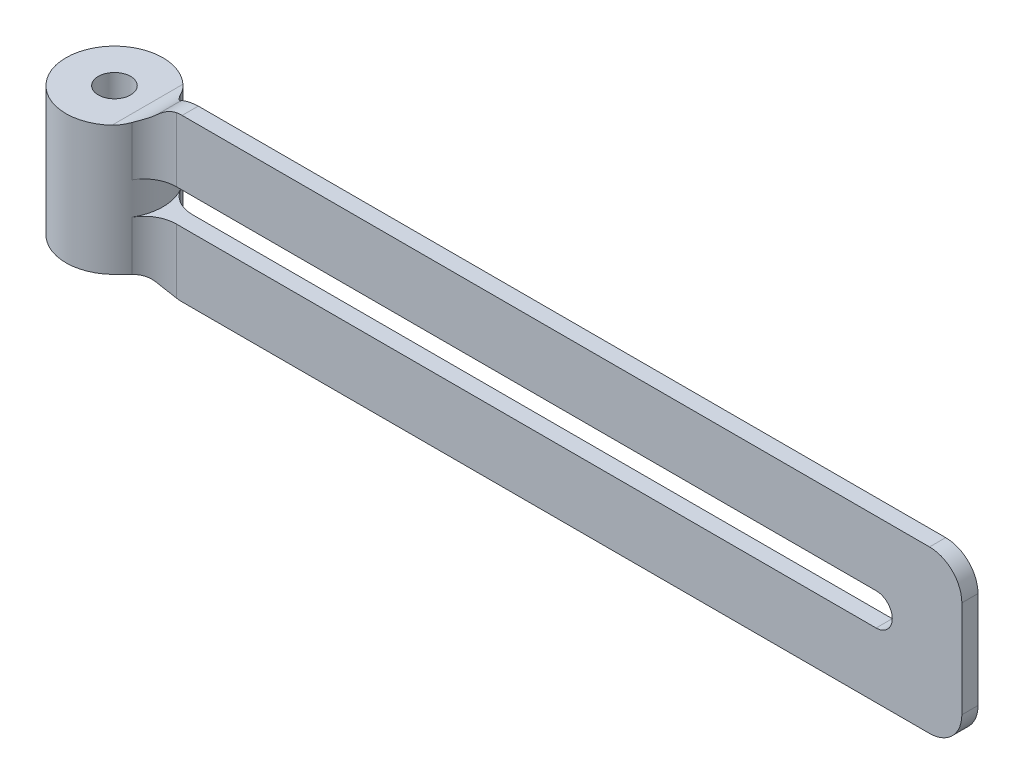
SolidWorks part; units mm, degrees
ref_plane "Front Plane" through (0, 0, 0) normal (0, 0, 1) x (1, 0, 0)
ref_plane "Top Plane" through (0, 0, 0) normal (0, 1, 0) x (1, 0, 0)
ref_plane "Right Plane" through (0, 0, 0) normal (1, 0, 0) x (0, 0, -1)
sketch "Sketch1" plane through (0, 0, 0) normal (0, 0, 1) x (1, 0, 0)
  line L1 (700, 2.5907) -> (0, 2.5907)
  line L2 (700, 2.5907) -> (700, 52.5907)
  line L3 (700, 52.5907) -> (0, 52.5907)
  line L4 (0, 2.5907) -> (0, 52.5907)
  dimension "D1" = 700
  dimension "D2" = 50
extrude "Boss-Extrude1" add sketch "Sketch1" along normal blind 5
fillet "Fillet1" radius 10 4 edges at (700, 2.5907, 2.5) (700, 52.5907, 2.5) (0, 2.5907, 2.5) (0, 52.5907, 2.5)
sketch "Sketch2" plane through (0, 0, 5) normal (0, 0, 1) x (1, 0, 0)
  line L0 (23.4634, 27.5907) -> (673.4634, 27.5907) construction
  line L1 (23.4634, 32.5907) -> (673.4634, 32.5907)
  line L2 (23.4634, 22.5907) -> (673.4634, 22.5907)
  line L3 (690, 52.5907) -> (10, 52.5907) construction
  arc A0 (23.4634, 32.5907) -> (23.4634, 22.5907) centre (23.4634, 27.5907) ccw
  arc A1 (673.4634, 22.5907) -> (673.4634, 32.5907) centre (673.4634, 27.5907) ccw
  point P2 (348.4634, 27.5907)
  dimension "D1" = 650
  dimension "D2" = 10
  dimension "D3" = 25
extrude "Cut-Extrude1" cut sketch "Sketch2" against normal blind 150
sketch "Sketch5" plane through (0, 0, 0) normal (0, 0, -1) x (-1, 0, 0)
  line L0 (-690, 52.5907) -> (-450, 52.5907)
  line L1 (-690, 52.5907) -> (-10, 52.5907) construction
  line L2 (-450, 52.5907) -> (-450, 2.5907)
  line L3 (-10, 2.5907) -> (-690, 2.5907) construction
  line L4 (-450, 2.5907) -> (-714.3563, 2.5907)
  line L5 (-714.3563, 2.5907) -> (-714.3563, 52.5907)
  line L6 (-714.3563, 52.5907) -> (-690, 52.5907)
  dimension "D1" = 240
extrude "Cut-Extrude3" cut sketch "Sketch5" against normal blind 10 flip side to cut
sketch "Sketch6" plane through (0, 52.5907, 0) normal (0, 1, 0) x (1, 0, 0)
  circle A0 centre (435.2098, -2.5) radius 5
  circle A1 centre (435.2098, -2.5) radius 15
  dimension "D1" = 10
  dimension "D2" = 10
extrude "Boss-Extrude3" add sketch "Sketch6" against normal blind 40 from offset 5 offset against normal yes
fillet "Fillet2" radius 10 2 edges at (450, 52.5907, 2.5) (450, 2.5907, 2.5)
fillet "Fillet3" radius 10 2 edges at (450, 47.5907, 2.5) (450, 7.5907, 2.5)
fillet "Fillet4" radius 10 4 edges at (450, 40.643, 5) (450, 14.5384, 5) (450, 40.643, 0) (450, 14.5384, 0)
